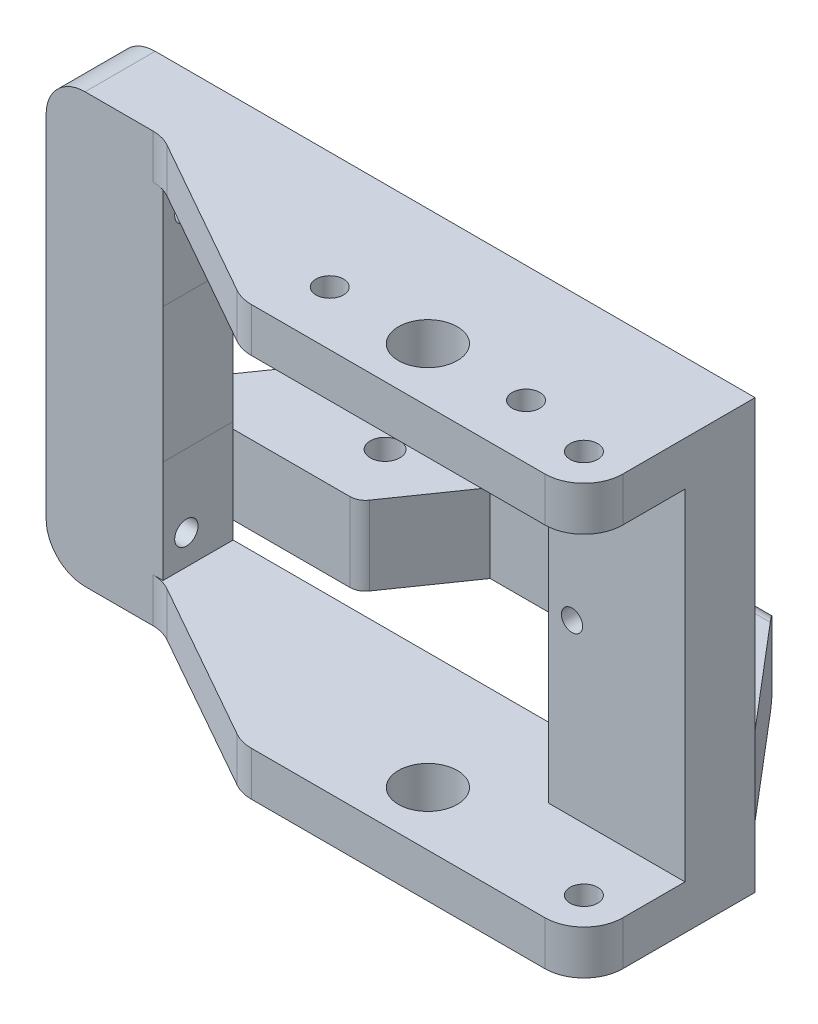
SolidWorks part; units mm, degrees
ref_plane "Front Plane" through (0, 0, 0) normal (0, 0, 1) x (1, 0, 0)
ref_plane "Top Plane" through (0, 0, 0) normal (0, 1, 0) x (1, 0, 0)
ref_plane "Right Plane" through (0, 0, 0) normal (1, 0, 0) x (0, 0, -1)
sketch "Sketch1" plane through (0, 0, 0) normal (0, 0, 1) x (1, 0, 0)
  line L1 (57.15, -34.925) -> (-57.15, -34.925)
  line L2 (57.15, -34.925) -> (57.15, 34.925)
  line L3 (57.15, 34.925) -> (-57.15, 34.925)
  line L4 (-57.15, -34.925) -> (-57.15, 34.925)
  line L5 (57.15, -34.925) -> (-57.15, 34.925) construction
  line L6 (57.15, 34.925) -> (-57.15, -34.925) construction
  point P0 (0, 0)
  dimension "D1" = 69.85
  dimension "D2" = 114.3
extrude "Boss-Extrude1" add sketch "Sketch1" along normal blind 57.15
sketch "Sketch2" plane through (0, 0, 57.15) normal (0, 0, 1) x (1, 0, 0)
  line L0 (-57.15, 34.925) -> (-57.15, -34.925) construction
  line L1 (57.15, -27.725) -> (-57.15, -27.725)
  line L2 (57.15, -27.725) -> (57.15, 27.725)
  line L3 (57.15, 27.725) -> (-57.15, 27.725)
  line L4 (-57.15, -27.725) -> (-57.15, 27.725)
  line L5 (57.15, -27.725) -> (-57.15, 27.725) construction
  line L6 (57.15, 27.725) -> (-57.15, -27.725) construction
  line L7 (57.15, 34.925) -> (-57.15, 34.925) construction
  point P0 (0, 0)
  dimension "D1" = 7.2
extrude "Cut-Extrude2" cut sketch "Sketch2" against normal blind 25.4
sketch "Sketch3" plane through (0, 0, 0) normal (0, 0, -1) x (-1, 0, 0)
  line L0 (-57.15, -34.925) -> (-57.15, 34.925) construction
  line L1 (57.15, 34.925) -> (-57.15, 34.925)
  line L2 (57.15, 34.925) -> (57.15, -12.065)
  line L3 (57.15, -12.065) -> (-57.15, -12.065)
  line L4 (-57.15, 34.925) -> (-57.15, -12.065)
  dimension "D1" = 46.99
extrude "Cut-Extrude3" cut sketch "Sketch3" against normal blind 20.32
sketch "Sketch5" plane through (0, -34.925, 0) normal (0, -1, 0) x (1, 0, 0)
  line L0 (-3.81, 10.79) -> (46.99, 10.79) construction
  line L1 (57.15, 20.32) -> (-57.15, 20.32) construction
  line L2 (57.15, 57.15) -> (57.15, 0) construction
  circle A0 centre (-3.81, 10.79) radius 2.415
  circle A1 centre (46.99, 10.79) radius 2.415
  dimension "D3" = 4.83
  dimension "D4" = 10.16
  dimension "D1" = 9.53
  dimension "D2" = 50.8
sketch "Sketch7" plane through (0, -34.925, 0) normal (0, -1, 0) x (1, 0, 0)
  line L0 (57.15, 57.15) -> (57.15, 0) construction
  line L2 (-57.15, 31.75) -> (57.15, 31.75) construction
  circle A0 centre (31.75, 39.37) radius 4.8
  dimension "D1" = 9.6
  dimension "D2" = 25.4
  dimension "D3" = 7.62
extrude "Cut-Extrude6" cut sketch "Sketch7" against normal up to surface (69.85 mm away) up to face at (0, 34.925, 38.735)
sketch "Sketch8" plane through (0, 34.925, 0) normal (0, 1, 0) x (1, 0, 0)
  line L0 (15.75, -39.37) -> (47.75, -39.37) construction
  line L1 (57.15, -31.75) -> (-57.15, -31.75) construction
  circle A0 centre (31.75, -39.37) radius 16 construction
  circle A1 centre (15.75, -39.37) radius 2.25
  circle A2 centre (47.75, -39.37) radius 2.25
  dimension "D1" = 32
  dimension "D2" = 4.5
  dimension "D3" = 0
sketch "Sketch9" plane through (0, 0, 31.75) normal (0, 0, 1) x (1, 0, 0)
  line L0 (57.15, 34.925) -> (-57.15, 34.925) construction
  line L5 (57.15, 27.725) -> (-57.15, 27.725) construction
  line L6 (-19.05, 27.725) -> (43.815, 27.725)
  line L7 (-19.05, 27.725) -> (-19.05, -27.725)
  line L8 (-19.05, -27.725) -> (43.815, -27.725)
  line L9 (43.815, 27.725) -> (43.815, -27.725)
  line L10 (-57.15, -27.725) -> (57.15, -27.725) construction
  line L11 (-57.15, 27.725) -> (-57.15, -27.725) construction
  line L12 (57.15, -27.725) -> (57.15, 27.725) construction
  line L13 (-57.15, -34.925) -> (-38.1, -34.925)
  line L14 (-57.15, -34.925) -> (-57.15, 34.925)
  line L15 (-57.15, 34.925) -> (-38.1, 34.925)
  line L16 (-38.1, -34.925) -> (-38.1, 34.925)
  line L17 (-57.15, -34.925) -> (-38.1, 34.925) construction
  line L18 (-57.15, 34.925) -> (-38.1, -34.925) construction
  line L19 (-57.15, -34.925) -> (57.15, -34.925) construction
  point P5 (-47.625, 0)
  dimension "D1" = 13.335
  dimension "25in" = 38.1
  dimension "D2" = 19.05
extrude "Cut-Extrude7" cut sketch "Sketch9" against normal through all both and the other way through all
extrude "Cut-Extrude8" cut sketch "Sketch8" against normal up to next
sketch "Sketch12" plane through (-19.05, 0, 0) normal (1, 0, 0) x (0, 0, -1)
  line L0 (-31.75, -27.725) -> (-31.75, 27.725) construction
  line L1 (-27.94, -22.86) -> (-27.94, 22.86) construction
  line L2 (-20.32, 27.725) -> (-20.32, -12.065) construction
  circle A0 centre (-27.94, -22.86) radius 1.905
  circle A1 centre (-27.94, 22.86) radius 1.905
  point P0 (-31.75, 0)
  point P8 (-27.94, 0)
  dimension "D1" = 3.81
  dimension "D2" = 7.62
  dimension "D3" = 45.72
extrude "Cut-Extrude10" cut sketch "Sketch12" against normal up to surface (19.05 mm away) up to face at (-38.1, -2.413, 33.274)
sketch "Sketch13" plane through (0, 34.925, 0) normal (0, 1, 0) x (1, 0, 0)
  line L0 (-38.1, -48.2242) -> (57.15, -48.2242)
  line L2 (57.15, -57.15) -> (-38.1, -57.15) construction
  line L3 (47.75, -39.37) -> (15.75, -39.37) construction
  line L4 (-38.1, -48.2242) -> (-38.1, -57.15)
  line L5 (-38.1, -57.15) -> (57.15, -57.15)
  line L6 (-38.1, -20.32) -> (-38.1, -57.15) construction
  line L7 (57.15, -57.15) -> (57.15, -20.32) construction
  line L8 (57.15, -48.2242) -> (57.15, -57.15)
extrude "Cut-Extrude12" cut sketch "Sketch13" against normal through all
sketch "Sketch14" plane through (43.815, 0, 0) normal (-1, 0, 0) x (0, 0, 1)
  line L0 (0, -27.725) -> (31.75, -27.725) construction
  line L1 (20.32, -12.065) -> (0, -12.065)
  line L2 (20.32, -12.065) -> (20.32, -27.725)
  line L3 (20.32, -27.725) -> (0, -27.725)
  line L4 (0, -12.065) -> (0, -27.725)
extrude "Boss-Extrude2" add sketch "Sketch14" along normal up to next
sketch "Sketch18" plane through (-38.1, 0, 0) normal (-1, 0, 0) x (0, 0, 1)
  line L0 (0, -34.925) -> (48.2242, -34.925) construction
  line L1 (20.32, -35.0627) -> (20.32, -24.9001)
  line L2 (20.32, -24.9001) -> (0, -24.9001)
  line L3 (0, -34.925) -> (0, -12.065) construction
  line L4 (0, -24.9001) -> (0, -34.925)
  line L5 (20.32, -34.925) -> (0, -34.925)
  point P0 (20.32, -34.925)
  point P1 (7.9478, 3.6724)
  line M3 (0, -34.925) -> (48.2242, -34.925)
  line M12 (0, -12.065) -> (0, -34.925)
extrude "Cut-Extrude20" cut sketch "Sketch5" against normal through all contours A0 | A1
extrude "Cut-Extrude21" cut sketch "Sketch18" against normal through all contours L1 L2 M12 M3 region at (-38.1, -29.9125, 10.16)
sketch "Sketch26" plane through (57.15, 0, 0) normal (1, 0, 0) x (0, 0, -1)
  line L28 (-48.2242, -34.925) -> (-20.32, -34.925)
  line L29 (-20.32, -34.925) -> (-20.32, -24.9001)
  line L30 (-20.32, -24.9001) -> (0, -24.9001)
  line L31 (0, -24.9001) -> (0, -12.065)
  line L32 (0, -12.065) -> (-20.32, -12.065)
  line L33 (-20.32, -12.065) -> (-20.32, 34.925)
  line L34 (-20.32, 34.925) -> (-48.2242, 34.925)
  line L35 (-48.2242, 34.925) -> (-48.2242, 27.725)
  line L36 (-48.2242, 27.725) -> (-31.75, 27.725)
  line L37 (-31.75, 27.725) -> (-31.75, -27.725)
  line L40 (-31.75, -27.725) -> (-48.2242, -27.725)
  line L41 (-48.2242, -27.725) -> (-48.2242, -34.925)
  line L42 (-48.2242, -34.925) -> (-20.32, -34.925)
  line L43 (-20.32, -34.925) -> (-20.32, -24.9001)
  line L44 (-20.32, -24.9001) -> (0, -24.9001)
  line L45 (0, -24.9001) -> (0, -12.065)
  line L46 (0, -12.065) -> (-20.32, -12.065)
  line L47 (-20.32, -12.065) -> (-20.32, 34.925)
  line L48 (-20.32, 34.925) -> (-48.2242, 34.925)
  line L49 (-48.2242, 34.925) -> (-48.2242, 27.725)
  line L50 (-48.2242, 27.725) -> (-31.75, 27.725)
  line L51 (-31.75, 27.725) -> (-31.75, -27.725)
  line L54 (-31.75, -27.725) -> (-48.2242, -27.725)
  line L55 (-48.2242, -27.725) -> (-48.2242, -34.925)
  dimension "D1" = 0
extrude "Boss-Extrude4" add sketch "Sketch26" along normal blind 8.89
sketch "Sketch31" plane through (0, 34.925, 0) normal (0, 1, 0) x (1, 0, 0)
  line L0 (66.04, -48.2242) -> (-38.1, -48.2242) construction
  line L1 (66.04, -20.32) -> (66.04, -48.2242) construction
  point P0 (59.69, -41.8742)
  dimension "D1" = 6.35
  dimension "D2" = 6.35
hole_wizard "#8 Clearance Hole1" positions "Sketch31" profile "Sketch30" hole size "#8" standard "ANSI Inch" end condition through all
sketch "Sketch30" plane through (59.69, 34.925, 41.8742) normal (1, 0, 0) x (0, 0, 1)
  line L0 (0, 0) -> (0, 69.85)
  line L1 (0, 69.85) -> (2.2479, 69.85)
  line L2 (2.2479, 69.85) -> (2.2479, 0)
  line L5 (2.2479, 0) -> (0, 0)
  line L11 (0, -6.35) -> (0, 107.95) construction
  dimension "Thru Hole Dia." = 4.4958
  dimension "Thru Hole Depth" = 69.85
sketch "Sketch38" plane through (0, 0, 31.75) normal (0, 0, 1) x (1, 0, 0)
  line L0 (43.815, -27.725) -> (43.815, 27.725) construction
  line L2 (47.625, 0) -> (43.815, 0) construction
  point P0 (47.625, 0)
  dimension "D1" = 3.81
hole_wizard "#8-32 Tapped Hole1" positions "Sketch38" profile "Sketch37" tap size "#8-32" standard "ANSI Inch" end condition through all
sketch "Sketch37" plane through (47.625, 0, 31.75) normal (1, 0, 0) x (0, -1, 0)
  line L0 (0, 0) -> (0, 31.75)
  line L1 (0, 31.75) -> (1.7272, 31.75)
  line L2 (1.7272, 31.75) -> (1.7272, 0)
  line L5 (1.7272, 0) -> (0, 0)
  line L11 (0, -6.35) -> (0, 107.95) construction
  dimension "Thru Tap Drill Dia." = 3.4544
  dimension "Thru Tap Drill Depth" = 31.75
cosmetic thread "Hole Thread1" parameters "D2"=4.1656
sketch "Sketch40" plane through (0, 0, 0) normal (0, 0, -1) x (-1, 0, 0)
  line L1 (-66.04, -12.065) -> (38.1, -12.065)
  line L2 (-66.04, -12.065) -> (-66.04, -24.9001)
  line L3 (-66.04, -24.9001) -> (38.1, -24.9001)
  line L4 (38.1, -12.065) -> (38.1, -24.9001)
extrude "Cut-Extrude22" cut sketch "Sketch40" against normal blind 1.27
sketch "Sketch42" plane through (0, 0, 20.32) normal (0, 0, -1) x (-1, 0, 0)
  line L0 (38.1, -12.065) -> (38.1, 34.925) construction
  line L1 (-66.04, -12.065) -> (38.1, -12.065)
  line L2 (-66.04, -12.065) -> (-66.04, 9.7254)
  line L3 (-66.04, 9.7254) -> (38.1, 9.7254)
  line L4 (38.1, -12.065) -> (38.1, 9.7254)
split line "Split Line1" [suppressed]
sketch "Sketch43" plane through (-19.05, 0, 0) normal (1, 0, 0) x (0, 0, -1)
  line L0 (-31.75, 27.725) -> (-31.75, -27.725) construction
  line L1 (-20.32, -10.9992) -> (-31.75, -10.9992)
  line L2 (-20.32, -10.9992) -> (-20.32, 10.945)
  line L3 (-20.32, 10.945) -> (-31.75, 10.945)
  line L4 (-31.75, -10.9992) -> (-31.75, 10.945)
  line L5 (-20.32, -10.9992) -> (-31.75, 10.945) construction
  line L6 (-20.32, 10.945) -> (-31.75, -10.9992) construction
  line L7 (-31.75, 0) -> (-20.32, 0) construction
  line L8 (-20.32, 27.725) -> (-20.32, -12.065) construction
  point P0 (-26.035, -0.0271)
split line "Split Line2"
sketch "Sketch44" plane through (43.815, 0, 0) normal (-1, 0, 0) x (0, 0, 1)
  line L0 (31.75, -27.725) -> (31.75, 27.725) construction
  line L1 (31.75, 6.35) -> (20.32, 6.35)
  line L2 (31.75, 6.35) -> (31.75, -6.35)
  line L3 (31.75, -6.35) -> (20.32, -6.35)
  line L4 (20.32, 6.35) -> (20.32, -6.35)
  line L5 (20.32, -12.065) -> (20.32, 27.725) construction
  point P8 (31.75, 0)
  point P9 (31.75, 0)
  dimension "D1" = 12.7
  dimension "D2" = 0
split line "Split Line3"
sketch "Sketch45" plane through (0, 0, 20.32) normal (0, 0, -1) x (-1, 0, 0)
  line L0 (38.1, -12.065) -> (38.1, 34.925) construction
  line L1 (-66.04, -12.065) -> (38.1, -12.065)
  line L2 (-66.04, -12.065) -> (-66.04, 4.495)
  line L3 (-66.04, 4.495) -> (38.1, 4.495)
  line L4 (38.1, -12.065) -> (38.1, 4.495)
  dimension "D1" = 16.56
split line "Split Line4"
sketch "Sketch47" plane through (0, 34.925, 0) normal (0, 1, 0) x (1, 0, 0)
  line L0 (-38.1, -31.75) -> (-19.05, -31.75)
  line L1 (-19.05, -31.75) -> (10.16, -48.2242)
  line L3 (-38.1, -31.75) -> (-38.1, -48.2242)
  line L4 (-38.1, -48.2242) -> (10.16, -48.2242)
  dimension "D1" = 48.26
extrude "Cut-Extrude24" cut sketch "Sketch47" against normal through all
fillet "Fillet3" radius 6.35 8 edges at (-38.1, 34.925, 26.035) (-38.1, -34.925, 26.035) (-19.05, -31.325, 31.75) (10.16, -31.325, 48.2242) (66.04, -31.325, 48.2242) (66.04, 31.325, 48.2242) (-19.05, 31.325, 31.75) (10.16, 31.325, 48.2242)
sketch "Sketch49" plane through (0, -24.9001, 0) normal (0, -1, 0) x (1, 0, 0)
  line L0 (-38.1, 20.32) -> (-32.3028, 20.32)
  line L1 (66.04, 20.32) -> (-31.75, 20.32) construction
  line L2 (-32.3028, 20.32) -> (-19.0502, 1.27)
  line L3 (66.04, 1.27) -> (-38.1, 1.27) construction
  line L4 (-19.0502, 1.27) -> (-38.1, 1.27)
  line L5 (-38.1, 1.27) -> (-38.1, 20.32)
  line L6 (1.325, 20.32) -> (10.16, 7.62)
  line L7 (10.16, 7.62) -> (33.02, 7.62)
  line L8 (33.02, 7.62) -> (43.815, 20.32)
  line L9 (43.815, 20.32) -> (1.325, 20.32)
  line L10 (66.04, 20.32) -> (49.8475, 1.27)
  line L11 (49.8475, 1.27) -> (66.04, 1.27)
  line L12 (66.04, 1.27) -> (66.04, 20.32)
  line L13 (-3.81, 10.79) -> (46.99, 10.79) construction
  line L14 (43.815, 20.32) -> (-19.05, 20.32) construction
  point P16 (21.59, 10.79)
  point P23 (21.59, 7.62)
  dimension "D5" = 6.35
extrude "Cut-Extrude25" cut sketch "Sketch49" against normal through all
fillet "Fillet4" radius 2.54 7 edges at (15.3986, -24.9001, 1.27) (49.8475, -18.4825, 1.27) (15.3986, -12.065, 1.27) (-19.0502, -18.4825, 1.27) (33.02, -18.4825, 7.62) (1.325, -18.4825, 20.32) (-32.3028, -18.4825, 20.32)
